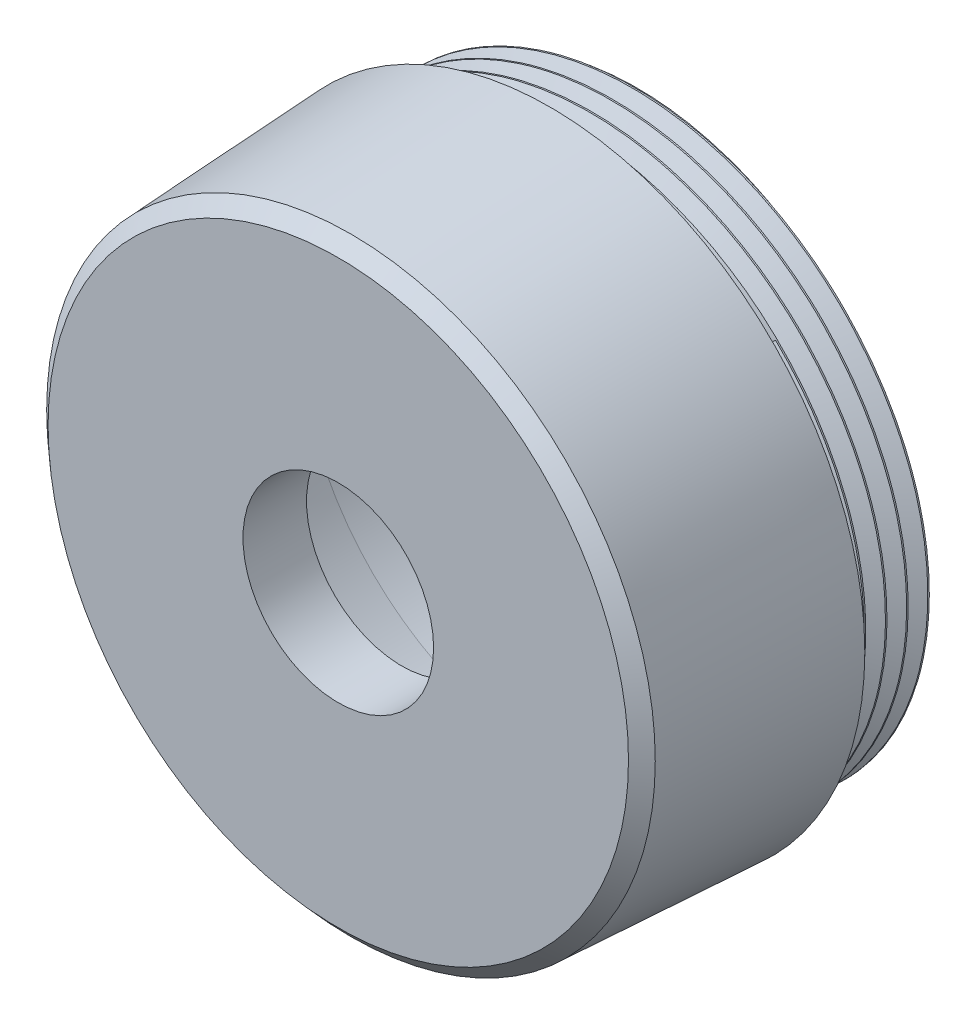
SolidWorks part; units mm, degrees
ref_plane "Front Plane" through (0, 0, 0) normal (0, 0, 1) x (1, 0, 0)
ref_plane "Top Plane" through (0, 0, 0) normal (0, 1, 0) x (1, 0, 0)
ref_plane "Right Plane" through (0, 0, 0) normal (1, 0, 0) x (0, 0, -1)
sketch "Sketch1" plane through (0, 0, 0) normal (0, 0, 1) x (1, 0, 0)
  circle A0 centre (0, 0) radius 7.43
  dimension "D1" = 14.86
extrude "Boss-Extrude3" add sketch "Sketch1" along normal blind 5 draft 3
shell "Shell1" thickness 1.5 removed face at (7.43, 0, 0)
sketch "Sketch3" plane through (0, 0, 0) normal (0, 0, -1) x (-1, 0, 0)
  circle A0 centre (0, 0) radius 5.9279 construction
  circle A1 centre (0, 0) radius 5.9279
  circle A2 centre (0, 0) radius 6.93
  dimension "D1" = 13.86
extrude "Boss-Extrude4" add sketch "Sketch3" along normal blind 2.2 separate body
combine bodies "Combine1" operation type add bodies to combine 103 104
sketch "Sketch5" plane through (0, 0, -2.2) normal (0, 0, -1) x (-1, 0, 0)
  circle A0 centre (0, 0) radius 6.93 construction
  circle A1 centre (0, 0) radius 6.93
curve "Helix/Spiral1" pitch 0.5 height 2 radius 6.93 centre (0, 0, -2.2) axis (0, 0, 1) start towards (0.7071, 0.7071, 0)
ref_plane "Plane1" through (4.9002, 4.9002, -2.2) normal (-0.7071, 0.7071, 0.0115) x (0.7072, 0.707, 0.0115)
sketch "Sketch6" plane through (4.9002, 4.9002, -2.2) normal (-0.7071, 0.7071, 0.0115) x (0.7072, 0.707, 0.0115)
  line L1 (-0.402, -0.007) -> (0.0224, -0.252)
  line L2 (0.0224, -0.252) -> (0.0224, 0.238)
  line L3 (0.0224, 0.238) -> (-0.402, -0.007)
  circle A0 centre (-0.1191, -0.007) radius 0.1415 construction
  dimension "D1" = 0.49
sweep "Cut-Sweep1" cut profiles "Sketch6" path "Helix/Spiral1" align with end faces yes
chamfer "Chamfer1" distance 0.3 angle 45 1 edges at (7.168, 0, 5) first distance on face at (7.168, 0, 5)
sketch "Sketch7" plane through (0, 0, 5) normal (0, 0, 1) x (1, 0, 0)
  circle A0 centre (0, 0) radius 2.25
  dimension "D1" = 4.5
extrude "Cut-Extrude1" cut sketch "Sketch7" against normal blind 6
